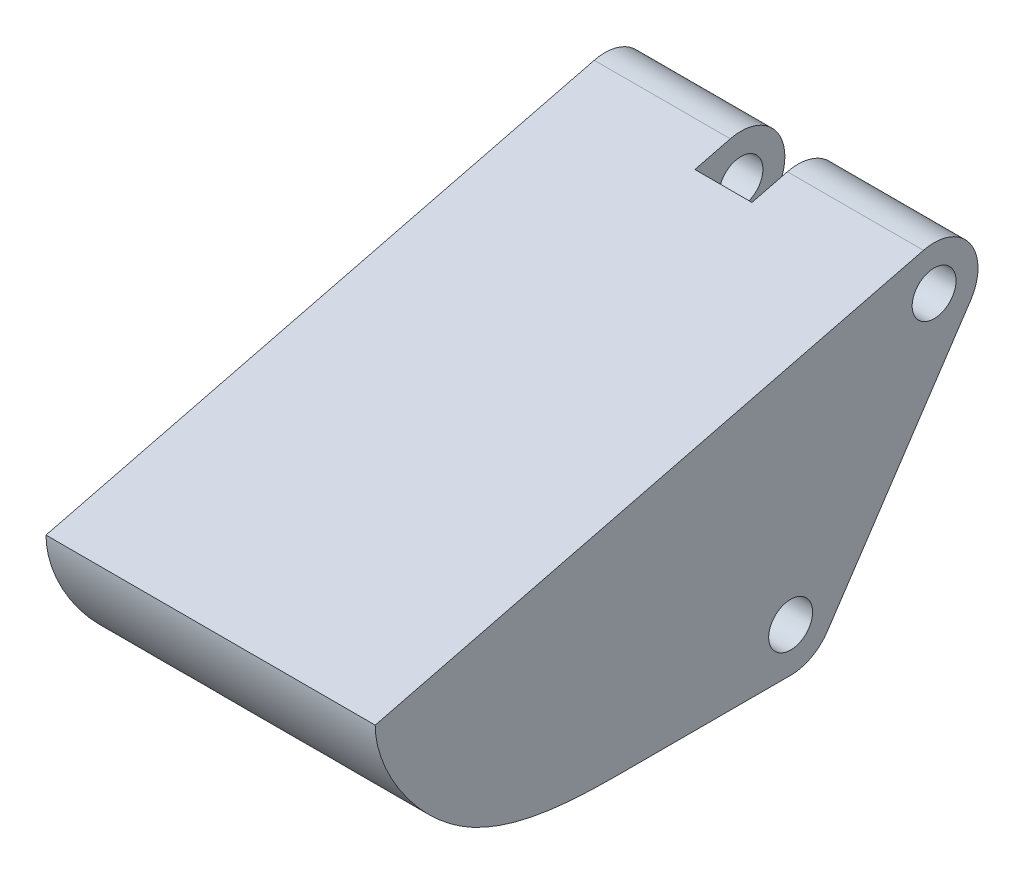
SolidWorks part; units mm, degrees
ref_plane "Front Plane" through (0, 0, 0) normal (0, 0, 1) x (1, 0, 0)
ref_plane "Top Plane" through (0, 0, 0) normal (0, 1, 0) x (1, 0, 0)
ref_plane "Right Plane" through (0, 0, 0) normal (1, 0, 0) x (0, 0, -1)
sketch "Sketch2" plane through (0, 0, 0) normal (1, 0, 0) x (0, 0, -1)
  line L0 (-5.0188, 6.2453) -> (-30, 0)
  line L1 (-18, -7.5) -> (-10, -7.5)
  line L5 (0, 7.5) -> (0, -7.5) construction
  line L6 (0, -7.5) -> (-10, -7.5) construction
  line L7 (-2.8696, 3.1956) -> (-9.4063, -6.6094)
  line L8 (-11.0704, -7.5) -> (-18, -7.5)
  line L9 (-30, 0) -> (0, 0) construction
  arc A0 (-9.4063, -6.6094) -> (-11.0704, -7.5) centre (-11.0704, -5.5) cw
  arc A1 (-2.8696, 3.1956) -> (-5.0188, 6.2453) centre (-4.5337, 4.305) ccw
  circle A2 centre (-4.5337, 4.305) radius 1
  circle A3 centre (-11.0704, -5.5) radius 1
  spline S0 degree 3 poles (-30, 0) (-30, -1.862) (-26.2969, -7.6709) (-20.2336, -7.5) (-18, -7.5) knots 0 0 0 0 0.469763 1 1 1 1
  point P0 (0, 0)
  point P13 (0, 0)
  dimension "D5" = 2
  dimension "D6" = 8
  dimension "D8" = 2
  dimension "D9" = 2
  dimension "D1" = 15
  dimension "D2" = 30
  dimension "D3" = 10
  dimension "D4" = 8
  dimension "D7" = 6
extrude "Boss-Extrude1" add sketch "Sketch2" along normal mid plane 15 contours L0 S0 L1 A0 L7 A1 region at (0, -1.3138, 15.9165)
ref_plane "Plane1" through (0, 6.305, 0) normal (0, 1, 0) x (1, 0, 0)
sketch "Sketch4" plane through (0, 6.305, 0) normal (0, 1, 0) x (1, 0, 0)
  line L0 (7.5, -2.5337) -> (-7.5, -2.5337) construction
  line L1 (1.3, -6.6337) -> (-1.3, -6.6337)
  line L2 (1.3, -6.6337) -> (1.3, -2.5337)
  line L3 (1.3, -2.5337) -> (-1.3, -2.5337)
  line L4 (-1.3, -6.6337) -> (-1.3, -2.5337)
  line L5 (1.3, -6.6337) -> (-1.3, -2.5337) construction
  line L6 (1.3, -2.5337) -> (-1.3, -6.6337) construction
  line L9 (-7.5, -3.7762) -> (7.5, -3.7762) construction
  line L10 (-7.5, -2.5337) -> (-7.5, -5.0188) construction
  line L11 (7.5, -5.0188) -> (7.5, -2.5337) construction
  point P0 (0, -4.5837)
  point P13 (0, -3.7762)
  dimension "D1" = 4.1
  dimension "D2" = 2.6
extrude "Cut-Extrude1" cut sketch "Sketch4" against normal blind 15
sketch "Sketch5" plane through (0, -7.5, 0) normal (0, -1, 0) x (1, 0, 0)
  line L1 (5, 7.0704) -> (-5, 7.0704)
  line L2 (5, 7.0704) -> (5, 14.0704)
  line L4 (-5, 7.0704) -> (-5, 14.0704)
  line L5 (5, 7.0704) -> (-5, 14.0704) construction
  line L6 (5, 14.0704) -> (-5, 7.0704) construction
  line L7 (7.5, 11.0704) -> (-7.5, 11.0704) construction
  arc A0 (-5, 14.0704) -> (5, 14.0704) centre (0, 10.7537) cw
  point P0 (0, 10.5704)
  dimension "D4" = 6
  dimension "D1" = 3
  dimension "D2" = 7
  dimension "D3" = 10
  dimension "D5" = 10
extrude "Cut-Extrude3" cut sketch "Sketch5" against normal blind 4
